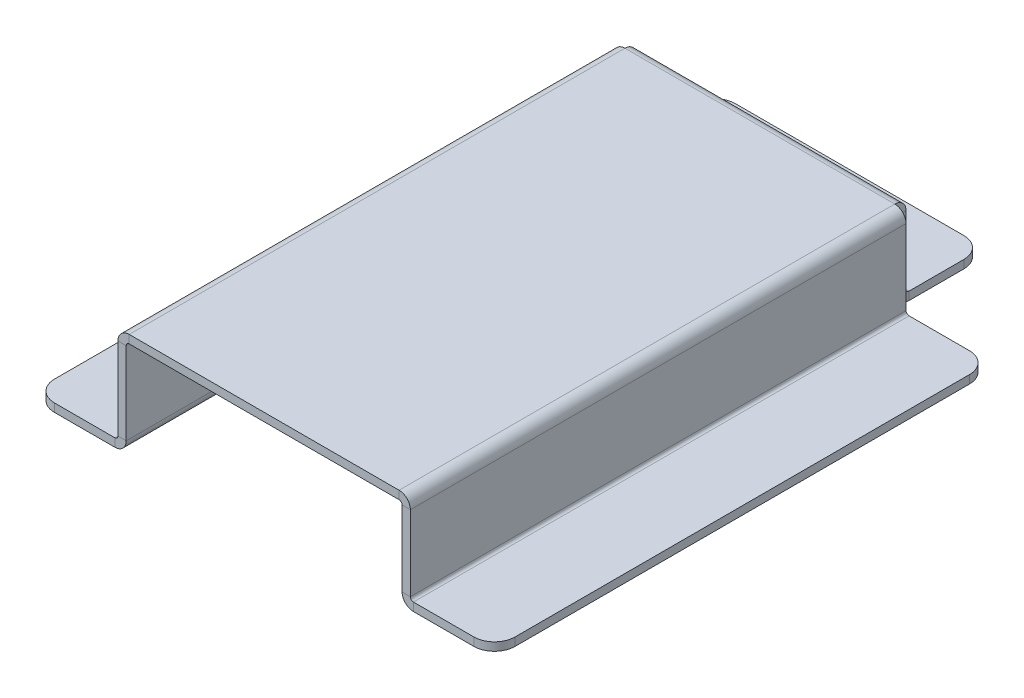
SolidWorks part; units mm, degrees
note: The reader was unsure of these and kept them because the rebuilt part matched: flange length of "Edge-Flange1", "Edge-Flange2", "Edge-Flange3", "Edge-Flange4", "Edge-Flange6", "Edge-Flange7".
ref_plane "Front Plane" through (0, 0, 0) normal (0, 0, 1) x (1, 0, 0)
ref_plane "Top Plane" through (0, 0, 0) normal (0, 1, 0) x (1, 0, 0)
ref_plane "Right Plane" through (0, 0, 0) normal (1, 0, 0) x (0, 0, -1)
sketch "Sketch3" plane through (0, 0, 0) normal (0, 1, 0) x (1, 0, 0)
  line L1 (-33.401, 60) -> (33.401, 60)
  line L2 (-33.401, 60) -> (-33.401, -60)
  line L3 (-33.401, -60) -> (33.401, -60)
  line L4 (33.401, 60) -> (33.401, -60)
  line L5 (-33.401, 60) -> (33.401, -60) construction
  line L6 (-33.401, -60) -> (33.401, 60) construction
  point P0 (0, 0)
  dimension "D1" = 66.802
  dimension "D2" = 120
base flange "Base-Flange1" sketch "Sketch3" thickness 1.99 reverse thickness direction no parameters "D1"=0.7366
edge flange "Edge-Flange1" sketch "Sketch10" flange angle 90 flange length 23.7 flange position material outside bend radius 0.7366 thickness 1.99 relief rectangular parameters "D6"=10
sketch "Sketch10" plane through (33.401, -1.99, 0) normal (1, 0, 0) x (0, 0, 1)
  line L2 (-60, 0) -> (-60, 21.71)
  line L3 (-60, 21.71) -> (60, 21.71)
  line L4 (60, 21.71) -> (60, 0)
  line L7 (60, 0) -> (-60, 0) construction
  line L8 (60, 0) -> (-60, 0)
bend "EdgeBend1" bend radius 0.7366 bend angle 90 parameters "D5"=1
edge flange "Edge-Flange2" sketch "Sketch13" flange angle 90 flange length 25.4 flange position material outside bend radius 0.7366 thickness 1.99 relief rectangular parameters "D6"=10
sketch "Sketch13" plane through (-33.401, -1.99, 0) normal (-1, 0, 0) x (0, 0, -1)
  line L0 (60, 0) -> (-60, 0) construction
  line L1 (60, 0) -> (-60, 0)
  line L2 (-60, 0) -> (-60, 23.41)
  line L3 (-60, 23.41) -> (60, 23.41)
  line L4 (60, 23.41) -> (60, 0)
bend "EdgeBend2" bend radius 0.7366 bend angle 90 parameters "D5"=2
edge flange "Edge-Flange3" sketch "Sketch16" flange angle 90 flange length 22.352 flange position material inside bend radius 0.7366 thickness 1.99 relief rectangular parameters "D6"=10
sketch "Sketch16" plane through (35.391, -23.7, 0) normal (0, -1, 0) x (0, 0, -1)
  line L0 (-60, 0) -> (60, 0) construction
  line L1 (-60, 0) -> (60, 0)
  line L2 (-60, 0) -> (-60, 20.362)
  line L3 (-60, 20.362) -> (60, 20.362)
  line L4 (60, 20.362) -> (60, 0)
bend "EdgeBend3" bend radius 0.7366 bend angle 90 parameters "D5"=3
edge flange "Edge-Flange4" sketch "Sketch19" flange angle 90 flange length 22.352 flange position material inside bend radius 0.7366 thickness 1.99 relief rectangular parameters "D6"=10
sketch "Sketch19" plane through (-35.391, -25.4, 0) normal (0, -1, 0) x (0, 0, 1)
  line L0 (-60, 0) -> (60, 0) construction
  line L1 (-60, 0) -> (60, 0)
  line L2 (-60, 0) -> (-60, 20.362)
  line L3 (-60, 20.362) -> (60, 20.362)
  line L4 (60, 20.362) -> (60, 0)
bend "EdgeBend4" bend radius 0.7366 bend angle 90 parameters "D5"=4
edge flange "Edge-Flange6" sketch "Sketch25" flange angle 90 flange length 19.98 flange position bend outside bend radius 0.7366 thickness 1.99 relief rectangular parameters "D6"=10
sketch "Sketch25" plane through (0, -1.99, -60) normal (0, 0, -1) x (1, 0, 0)
  line L0 (32.6644, 0) -> (-32.6644, 0) construction
  line L1 (32.6644, 0) -> (-32.6644, 0)
  line L2 (-32.6644, 0) -> (-32.6644, 17.99)
  line L3 (-32.6644, 17.99) -> (32.6644, 17.99)
  line L4 (32.6644, 17.99) -> (32.6644, 0)
bend "EdgeBend6" bend radius 0.7366 bend angle 90 parameters "D5"=5
edge flange "Edge-Flange7" sketch "Sketch28" flange angle 90 flange length 21 flange position material outside bend radius 0.7366 thickness 1.99 relief rectangular parameters "D6"=10
sketch "Sketch28" plane through (0, -19.98, -62.7266) normal (0, -1, 0) x (-1, 0, 0)
  line L2 (-32.6644, 0) -> (-32.6644, 19.01)
  line L3 (-32.6644, 19.01) -> (32.6644, 19.01)
  line L4 (32.6644, 19.01) -> (32.6644, 0)
  line L7 (-32.6644, 0) -> (32.6644, 0) construction
  line L8 (-32.6644, 0) -> (32.6644, 0)
bend "EdgeBend7" bend radius 0.7366 bend angle 90 parameters "D5"=6
fillet "Fillet1" radius 5 6 edges at (55.753, -22.705, 60) (55.753, -22.705, -60) (32.6644, -20.975, -81.7366) (-32.6644, -20.975, -81.7366) (-55.753, -24.405, -60) (-55.753, -24.405, 60)
sketch "Bend-Lines1" [suppressed] plane through (0, 0, 0) normal (0, 1, 0) x (1, 0, 0)
sketch "Bounding-Box1" [suppressed] plane through (0, 0, 0) normal (0, 1, 0) x (1, 0, 0)
sheet metal parameters "Sheet-Metal1" thickness 1.99 parameters "D1"=0.7366
flat pattern "Flat-Pattern1" [suppressed]
sketch "Bend-Lines2" plane through (0, 0, 0) normal (0, 1, 0) x (1, 0, 0)
sketch3d "Bounding-Box2" [suppressed]
  line L0 (-33.401, -20, 0) -> (33.401, -20, 0) construction
  line L1 (-33.401, 20, 0) -> (33.401, 20, 0) construction
  line L2 (-33.401, -20, 0) -> (-33.401, 20, 0) construction
  line L3 (33.401, -20, 0) -> (33.401, 20, 0) construction
sheet metal parameters "Sheet-Metal2" thickness 1.99 parameters "D1"=0.7366
flat pattern "Flat-Pattern1"
sketch "Bend-Lines2" plane through (0, 0, 0) normal (0, 1, 0) x (1, 0, 0)
  line L0 (32.0344, -20) -> (32.0344, 20) construction
  line L1 (32.0344, -20) -> (32.0344, 20) construction
sketch3d "Bounding-Box2" [suppressed]
  line L0 (56.0678, -20, 0) -> (-33.401, -20, 0) construction
  line L1 (56.0678, 20, 0) -> (-33.401, 20, 0) construction
  line L2 (56.0678, -20, 0) -> (56.0678, 20, 0) construction
  line L3 (-33.401, -20, 0) -> (-33.401, 20, 0) construction
bend of the flat pattern "Flatten-<EdgeBend1>1"
sheet metal parameters "Sheet-Metal3" thickness 1.99 parameters "D1"=0.7366
flat pattern "Flat-Pattern1"
sketch "Bend-Lines2" plane through (0, 0, 0) normal (0, 1, 0) x (1, 0, 0)
  line L0 (32.0344, -20) -> (32.0344, 20) construction
  line L1 (32.0344, -20) -> (32.0344, 20) construction
  line L2 (-32.0344, 20) -> (-32.0344, -20) construction
  line L3 (-32.0344, 20) -> (-32.0344, -20) construction
sketch3d "Bounding-Box2" [suppressed]
  line L0 (56.0678, -20, 0) -> (-56.0678, -20, 0) construction
  line L1 (56.0678, 20, 0) -> (-56.0678, 20, 0) construction
  line L2 (56.0678, -20, 0) -> (56.0678, 20, 0) construction
  line L3 (-56.0678, -20, 0) -> (-56.0678, 20, 0) construction
bend of the flat pattern "Flatten-<EdgeBend1>1"
bend of the flat pattern "Flatten-<EdgeBend2>1"
sheet metal parameters "Sheet-Metal4" thickness 1.99 parameters "D1"=0.7366
flat pattern "Flat-Pattern1"
sketch "Bend-Lines2" plane through (0, 0, 0) normal (0, 1, 0) x (1, 0, 0)
  line L0 (32.0344, -20) -> (32.0344, 20) construction
  line L1 (32.0344, -20) -> (32.0344, 20) construction
  line L2 (-32.0344, 20) -> (-32.0344, -20) construction
  line L3 (-32.0344, 20) -> (-32.0344, -20) construction
  line L4 (54.7012, -20) -> (54.7012, 20) construction
  line L5 (54.7012, -20) -> (54.7012, 20) construction
sketch3d "Bounding-Box2" [suppressed]
  line L0 (73.6546, -20, 0) -> (-56.0678, -20, 0) construction
  line L1 (73.6546, 20, 0) -> (-56.0678, 20, 0) construction
  line L2 (73.6546, -20, 0) -> (73.6546, 20, 0) construction
  line L3 (-56.0678, -20, 0) -> (-56.0678, 20, 0) construction
bend of the flat pattern "Flatten-<EdgeBend1>1"
bend of the flat pattern "Flatten-<EdgeBend2>1"
bend of the flat pattern "Flatten-<EdgeBend3>1"
sheet metal parameters "Sheet-Metal5" thickness 1.99 parameters "D1"=0.7366
flat pattern "Flat-Pattern1"
sketch "Bend-Lines2" plane through (0, 0, 0) normal (0, 1, 0) x (1, 0, 0)
  line L0 (32.0344, -60) -> (32.0344, 60) construction
  line L1 (32.0344, -60) -> (32.0344, 60) construction
  line L2 (-32.0344, 60) -> (-32.0344, -60) construction
  line L3 (-32.0344, 60) -> (-32.0344, -60) construction
  line L4 (54.7012, -60) -> (54.7012, 60) construction
  line L5 (54.7012, -60) -> (54.7012, 60) construction
  line L6 (-54.7012, 60) -> (-54.7012, -60) construction
  line L7 (-54.7012, 60) -> (-54.7012, -60) construction
sketch3d "Bounding-Box2" [suppressed]
  line L0 (73.6546, -60, 0) -> (-73.6546, -60, 0) construction
  line L1 (73.6546, 60, 0) -> (-73.6546, 60, 0) construction
  line L2 (73.6546, -60, 0) -> (73.6546, 60, 0) construction
  line L3 (-73.6546, -60, 0) -> (-73.6546, 60, 0) construction
bend of the flat pattern "Flatten-<EdgeBend1>1"
bend of the flat pattern "Flatten-<EdgeBend2>1"
bend of the flat pattern "Flatten-<EdgeBend3>1"
bend of the flat pattern "Flatten-<EdgeBend4>1"
sheet metal parameters "Sheet-Metal7" thickness 1.99 parameters "D1"=0.7366
flat pattern "Flat-Pattern1"
sketch "Bend-Lines2" plane through (0, 0, 0) normal (0, 1, 0) x (1, 0, 0)
  line L0 (32.0344, -60) -> (32.0344, 60) construction
  line L1 (32.0344, -60) -> (32.0344, 60) construction
  line L2 (-32.0344, 60) -> (-32.0344, -60) construction
  line L3 (-32.0344, 60) -> (-32.0344, -60) construction
  line L4 (54.7012, -60) -> (54.7012, 60) construction
  line L5 (54.7012, -60) -> (54.7012, 60) construction
  line L6 (-54.7012, 60) -> (-54.7012, -60) construction
  line L7 (-54.7012, 60) -> (-54.7012, -60) construction
  line L8 (30.6744, 61.36) -> (-30.6744, 61.36) construction
  line L9 (30.6744, 61.36) -> (-30.6744, 61.36) construction
sketch3d "Bounding-Box2" [suppressed]
  line L0 (73.6546, -60, 0) -> (-73.6546, -60, 0) construction
  line L1 (73.6546, 85.3934, 0) -> (-73.6546, 85.3934, 0) construction
  line L2 (73.6546, -60, 0) -> (73.6546, 85.3934, 0) construction
  line L3 (-73.6546, -60, 0) -> (-73.6546, 85.3934, 0) construction
bend of the flat pattern "Flatten-<EdgeBend1>1"
bend of the flat pattern "Flatten-<EdgeBend2>1"
bend of the flat pattern "Flatten-<EdgeBend3>1"
bend of the flat pattern "Flatten-<EdgeBend4>1"
bend of the flat pattern "Flatten-<EdgeBend6>1"
sheet metal parameters "Sheet-Metal8" thickness 1.99 parameters "D1"=0.7366
flat pattern "Flat-Pattern1"
sketch "Bend-Lines2" plane through (0, 0, 0) normal (0, 1, 0) x (1, 0, 0)
  line L0 (34.0244, -60) -> (34.0244, 60) construction
  line L1 (34.0244, -60) -> (34.0244, 60) construction
  line L2 (-34.0244, 60) -> (-34.0244, -60) construction
  line L3 (-34.0244, 60) -> (-34.0244, -60) construction
  line L4 (54.9912, -60) -> (54.9912, 60) construction
  line L5 (54.9912, -60) -> (54.9912, 60) construction
  line L6 (-56.6912, 60) -> (-56.6912, -60) construction
  line L7 (-56.6912, 60) -> (-56.6912, -60) construction
  line L8 (32.6644, 61.36) -> (-32.6644, 61.36) construction
  line L9 (32.6644, 61.36) -> (-32.6644, 61.36) construction
  line L10 (32.6644, 80.5968) -> (-32.6644, 80.5968) construction
  line L11 (32.6644, 80.5968) -> (-32.6644, 80.5968) construction
sketch3d "Bounding-Box2" [suppressed]
  line L0 (75.9766, 100.2302, 0) -> (75.9766, -60, 0) construction
  line L1 (-77.6766, 100.2302, 0) -> (-77.6766, -60, 0) construction
  line L2 (75.9766, 100.2302, 0) -> (-77.6766, 100.2302, 0) construction
  line L3 (75.9766, -60, 0) -> (-77.6766, -60, 0) construction
bend of the flat pattern "Flatten-<EdgeBend1>1"
bend of the flat pattern "Flatten-<EdgeBend2>1"
bend of the flat pattern "Flatten-<EdgeBend3>1"
bend of the flat pattern "Flatten-<EdgeBend4>1"
bend of the flat pattern "Flatten-<EdgeBend6>1"
bend of the flat pattern "Flatten-<EdgeBend7>1"
sketch "Sheet Metal Gusset1-Outline1" plane through (0, 0, 0) normal (0, 1, 0) x (1, 0, 0)
  line L0 (64.6627, 47.5) -> (54.3612, 47.5) construction
  line L1 (64.6627, 52.5) -> (54.3612, 52.5) construction
  line L2 (64.6627, 47.5) -> (54.3612, 47.5)
  line L3 (64.6627, 52.5) -> (54.3612, 52.5)
  line L4 (41.3397, 47.5) -> (51.6412, 47.5) construction
  line L5 (41.3397, 52.5) -> (51.6412, 52.5) construction
  line L6 (41.3397, 47.5) -> (51.6412, 47.5)
  line L7 (41.3397, 52.5) -> (51.6412, 52.5)
  line L8 (54.3612, 47.5) -> (51.6412, 47.5)
  line L9 (54.3612, 47.5) -> (51.6412, 52.5)
  line L10 (54.3612, 52.5) -> (51.6412, 52.5)
  ellipse E0 centre (64.6627, 50) end of major axis (61.1271, 50) minor radius 2.5 (64.6627, 47.5) -> (64.6627, 52.5) ccw construction
  ellipse E1 centre (64.6627, 50) end of major axis (61.1271, 50) minor radius 2.5 (64.6627, 47.5) -> (64.6627, 52.5) ccw
  ellipse E2 centre (41.3397, 50) end of major axis (37.8042, 50) minor radius 2.5 (41.3397, 52.5) -> (41.3397, 47.5) ccw construction
  ellipse E3 centre (41.3397, 50) end of major axis (37.8042, 50) minor radius 2.5 (41.3397, 52.5) -> (41.3397, 47.5) ccw
  point P26 (53.0012, 50)
